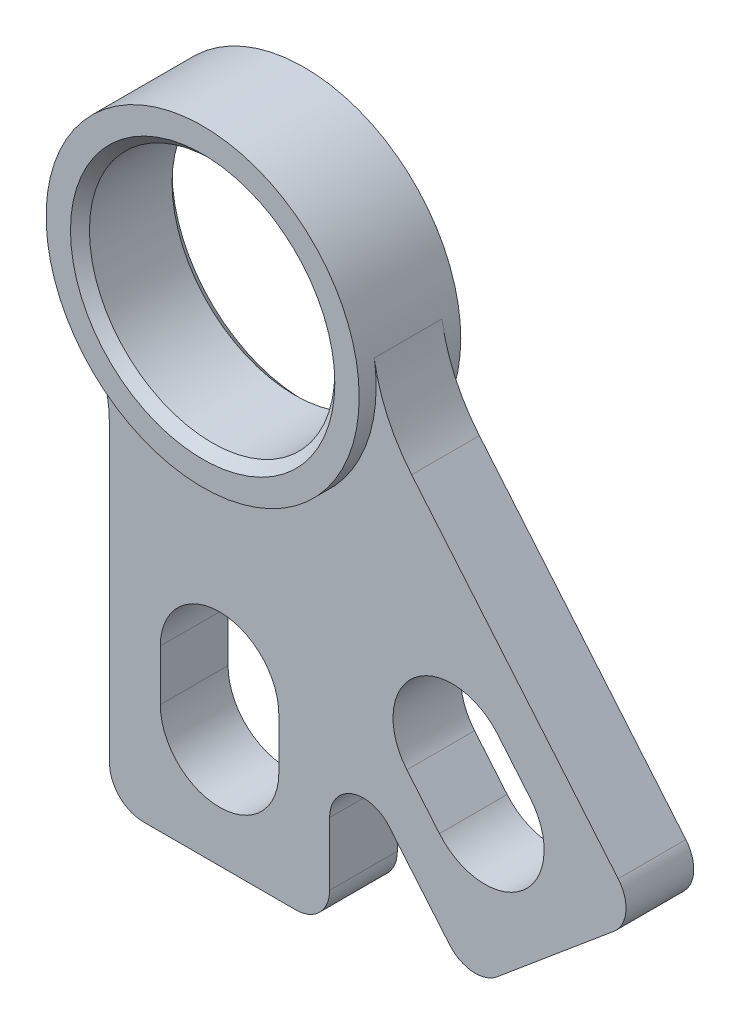
SolidWorks part; units mm, degrees
material "AISI 4130 Steel, annealed at 865C"
ref_plane "X-Y Datum" through (0, 0, 0) normal (0, 0, 1) x (1, 0, 0)
ref_plane "X-Z Datum" through (0, 0, 0) normal (0, 1, 0) x (1, 0, 0)
ref_plane "Y-Z Datum" through (0, 0, 0) normal (1, 0, 0) x (0, 0, -1)
sketch "Sketch1" plane through (0, 0, 0) normal (0, 0, 1) x (1, 0, 0)
  line L0 (0, -35.8956) -> (0, -31.1331) construction
  line L1 (-5.5562, -35.8956) -> (-5.5562, -31.1331)
  line L2 (5.5563, -35.8956) -> (5.5563, -31.1331)
  line L3 (24.8797, -29.7119) -> (21.8222, -26.0605) construction
  line L4 (20.6198, -33.2791) -> (17.5622, -29.6277)
  line L5 (29.1397, -26.1448) -> (26.0821, -22.4934)
  line L6 (-10.3187, -15.7343) -> (-10.3187, -46.2143)
  line L7 (-10.3187, -46.2143) -> (10.3188, -46.2143)
  line L10 (23.5931, -44.248) -> (39.4158, -30.9986)
  line L11 (39.4158, -30.9986) -> (18.0129, -5.4388)
  line L12 (10.3188, -46.2143) -> (10.3188, -28.3955)
  line L14 (0, -41.4518) -> (0, -46.2143) construction
  line L15 (28.4469, -33.9719) -> (31.5044, -37.6233) construction
  line L16 (27.6109, -24.3191) -> (31.2623, -21.2615) construction
  line L17 (-5.5562, -33.5143) -> (-10.3187, -33.5143) construction
  line L18 (-10.3187, -20.8143) -> (10.3188, -20.8143) construction
  line L19 (10.3188, -20.8143) -> (10.3188, -46.2143) construction
  line L20 (5.5563, -33.5143) -> (10.3188, -33.5143) construction
  line L21 (0, -25.5768) -> (0, -20.8143) construction
  line L22 (23.5931, -44.248) -> (7.2861, -24.7739) construction
  line L23 (7.2861, -24.7739) -> (23.1088, -11.5245) construction
  line L24 (19.091, -31.4534) -> (15.4396, -34.5109) construction
  line L25 (18.255, -21.8006) -> (15.1975, -18.1492) construction
  line L29 (23.5931, -44.248) -> (10.3188, -28.3955)
  line L31 (0, -347.9572) -> (0, 0) construction
  line L32 (202.4259, -241.7417) -> (0, 0) construction
  circle A0 centre (0, 0) radius 11.5062
  arc A1 (-5.5562, -35.8956) -> (5.5563, -35.8956) centre (0, -35.8956) ccw
  arc A2 (5.5563, -31.1331) -> (-5.5562, -31.1331) centre (0, -31.1331) ccw
  arc A3 (20.6198, -33.2791) -> (29.1397, -26.1448) centre (24.8797, -29.7119) ccw
  arc A4 (26.0821, -22.4934) -> (17.5622, -29.6277) centre (21.8222, -26.0605) ccw
  arc A5 (14.5025, 2.2837) -> (-12.5852, -7.5598) centre (0, 0) ccw
  arc A6 (18.0129, -5.4388) -> (14.5025, 2.2837) centre (30.1843, 4.7531) cw
  arc A7 (-10.3187, -15.7343) -> (-12.5852, -7.5598) centre (-26.1937, -15.7343) ccw
  arc A14 (-12.5852, -7.5598) -> (14.5025, 2.2837) centre (0, 0) ccw
  point P5 (0, -33.5143)
  point P11 (23.3509, -27.8862)
  point P24 (31.5044, -37.6233)
  point P39 (28.4469, -33.9719)
  dimension "D1" = 23.0124
  dimension "D2" = 3.175
  dimension "D8" = 15.875
  dimension "D6" = 7.9375
  dimension "D7" = 5.08
  dimension "D3" = 20.6375
  dimension "D4" = 4.7625
  dimension "D5" = 25.4
extrude "Boss-Extrude2" add sketch "Sketch1" along normal mid plane 9.525 contours A5 A14 A0 region at (-4.8724, 13.4081, 0)
extrude "Boss-Extrude3" add sketch "Sketch1<4>" along normal mid plane 6.35 contours L29 L10 L11 A6 A14 A7 L6 L7 A4 L5 A3 L4 A2 L2 A1 L1 region at (10.3663, -26.2093, 0)
sketch "Sketch1<4>" plane through (0, 0, 0) normal (0, 0, 1) x (1, 0, 0) same geometry as "Sketch1"
fillet "Fillet1" radius 3.175 5 edges at (-10.3187, -46.2143, 0) (39.4158, -30.9986, 0) (10.3188, -28.3955, 0) (23.5931, -44.248, 0) (10.3188, -46.2143, 0)
chamfer "Chamfer1" distance 0.889 angle 45 2 edges at (11.5062, 0, -4.7625) (11.5062, 0, 4.7625)
fillet "Fillet2" [suppressed] radius 1.27
